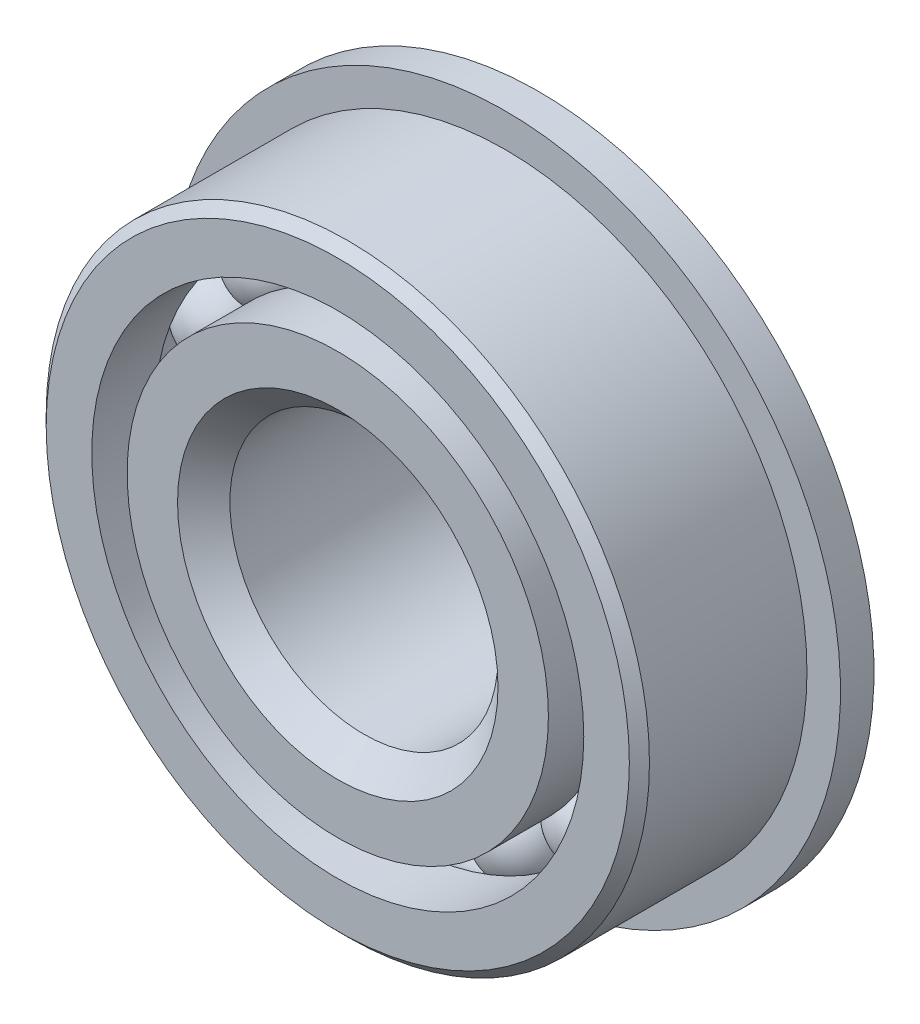
SolidWorks part; units mm, degrees
ref_plane "Front Plane" through (0, 0, 0) normal (0, 0, 1) x (1, 0, 0)
ref_plane "Top Plane" through (0, 0, 0) normal (0, 1, 0) x (1, 0, 0)
ref_plane "Right Plane" through (0, 0, 0) normal (1, 0, 0) x (0, 0, -1)
sketch "Sketch1" plane through (0, 0, 0) normal (1, 0, 0) x (0, 0, -1)
  line L0 (-4.7625, 0) -> (4.7625, 0) construction
  line L1 (0, 14.2875) -> (0, -14.2875) construction
  line L2 (4.2863, 14.2875) -> (-4.2863, 14.2875)
  line L3 (-4.2863, 14.2875) -> (-4.7625, 13.8112)
  line L4 (-4.7625, 13.8112) -> (-4.7625, 11.6522)
  line L5 (-4.7625, 11.6522) -> (-1.799, 11.6522)
  line L6 (4.7625, 11.6522) -> (1.799, 11.6522)
  line L7 (4.7625, 13.8112) -> (4.7625, 11.6522)
  line L8 (4.2863, 14.2875) -> (4.7625, 13.8112)
  line L9 (0, 14.2875) -> (0, 10.8148) construction
  line L11 (4.7625, 0) -> (6.35, 0) construction
  arc A0 (-1.799, 11.6522) -> (1.799, 11.6522) centre (0, 10.8148) cw
  circle A1 centre (0, 10.8148) radius 1.9844 construction
  point P14 (0, 6.35)
  dimension "D3" = 3.9688
  dimension "D1" = 45
  dimension "Width" = 9.525
  dimension "OD" = 28.575
  dimension "D2" = 0.4763
  dimension "Shaft Dia" = 12.7
  dimension "D4" = 0.8374
  dimension "D5" = 3.4727
  dimension "Total Wd" = 11.1125
revolve "Revolve1" add sketch "Sketch1" angle 360 about L0
sketch "Sketch2" plane through (0, 0, 0) normal (1, 0, 0) x (0, 0, -1)
  line L0 (-4.7625, 9.9775) -> (-1.799, 9.9775)
  line L1 (-4.7625, 13.8112) -> (-4.7625, -13.8112) construction
  line L2 (-4.7625, 9.9775) -> (-4.7625, 8.7839)
  line L3 (-4.7625, 8.7839) -> (-3.5689, 7.5902)
  line L4 (-3.5689, 7.5902) -> (0, 7.5902)
  line L5 (0, 14.2875) -> (0, -14.2875) construction
  line L6 (0, 7.5902) -> (0, 8.8305)
  line L7 (0, 8.8305) -> (0, 6.35) construction
  line L8 (-4.7625, 9.9775) -> (-4.7625, 7.5902) construction
  line L9 (-4.7625, 7.5902) -> (-3.5689, 7.5902) construction
  arc A0 (-1.799, 9.9775) -> (0, 8.8305) centre (0, 10.8148) ccw
  arc A1 (1.799, 11.6522) -> (-1.799, 11.6522) centre (0, 10.8148) ccw construction
  circle A2 centre (0, 10.8148) radius 1.9844 construction
  dimension "D1" = 45
revolve "Revolve2" add sketch "Sketch2" angle 360 about L0
sketch "Sketch3" plane through (0, 0, 0) normal (1, 0, 0) x (0, 0, -1)
  line L0 (-4.7625, 8.7839) -> (-3.5689, 7.5902)
  line L1 (-3.5689, 7.5902) -> (0, 7.5902)
  line L2 (0, 7.5902) -> (0, 8.8305)
  line L3 (-4.7625, 8.7839) -> (-4.7625, 7.5902)
  line L4 (-4.7625, 9.9775) -> (-4.7625, 7.5902) construction
  line L5 (-4.7625, 7.5902) -> (-3.5223, 6.35)
  line L6 (-3.5223, 6.35) -> (5.8737, 6.35)
  line L8 (5.8737, 6.35) -> (6.35, 6.8263)
  line L10 (6.35, 6.8263) -> (6.35, 9.9775)
  line L11 (6.35, 9.9775) -> (1.799, 9.9775)
  line L13 (4.2863, 14.2875) -> (4.7625, 13.8112) construction
  circle A0 centre (0, 10.8148) radius 1.9844 construction
  arc A1 (1.799, 9.9775) -> (0, 8.8305) centre (0, 10.8148) cw
revolve "Revolve3" add sketch "Sketch3" angle 360 about L0
sketch "Sketch4" plane through (0, 0, 0) normal (1, 0, 0) x (0, 0, -1)
  line L0 (-1.9844, 10.8148) -> (1.9844, 10.8148)
  circle A1 centre (0, 10.8148) radius 1.9844 construction
  arc A2 (-1.9844, 10.8148) -> (1.9844, 10.8148) centre (0, 10.8148) cw
  arc A3 (1.799, 11.6522) -> (-1.799, 11.6522) centre (0, 10.8148) ccw construction
revolve "Revolve4" add sketch "Sketch4" angle 360 about L0
ref_axis "Axis1" through (0, 0, -4.7625) along (0, 0, 1)
pattern_circular "CirPattern1" count 16 every 22.5 about axis through (0, 0, -4.7625) along (0, 0, 1) of bodies 104
sketch "Sketch5" plane through (0, 0, 0) normal (1, 0, 0) x (0, 0, -1)
  line L0 (4.7625, 13.8112) -> (4.7625, 11.6522) construction
  line L1 (4.7625, 12.7317) -> (3.175, 12.7317)
  line L2 (4.7625, 12.7317) -> (4.7625, 15.875)
  line L3 (4.7625, 15.875) -> (3.175, 15.875)
  line L4 (3.175, 12.7317) -> (3.175, 15.875)
  line L5 (6.35, 0) -> (-4.7625, 0) construction
  dimension "Flange Thickness" = 1.5875
  dimension "Flange OD" = 31.75
revolve "Revolve5" add sketch "Sketch5" angle 360 about L5
equation "\"D2@Sketch1\" = \"Width@Sketch1\"*.05"
equation "\"D4@Sketch1\" = (((\"OD@Sketch1\"-\"Width@Sketch1\")/2)/3.25)/3.5"
equation "\"D2@CirPattern1\" = 360/\"Balls@CirPattern1\""
equation "\"D5@Sketch1\" = \"D3@Sketch1\" * 7/8"
